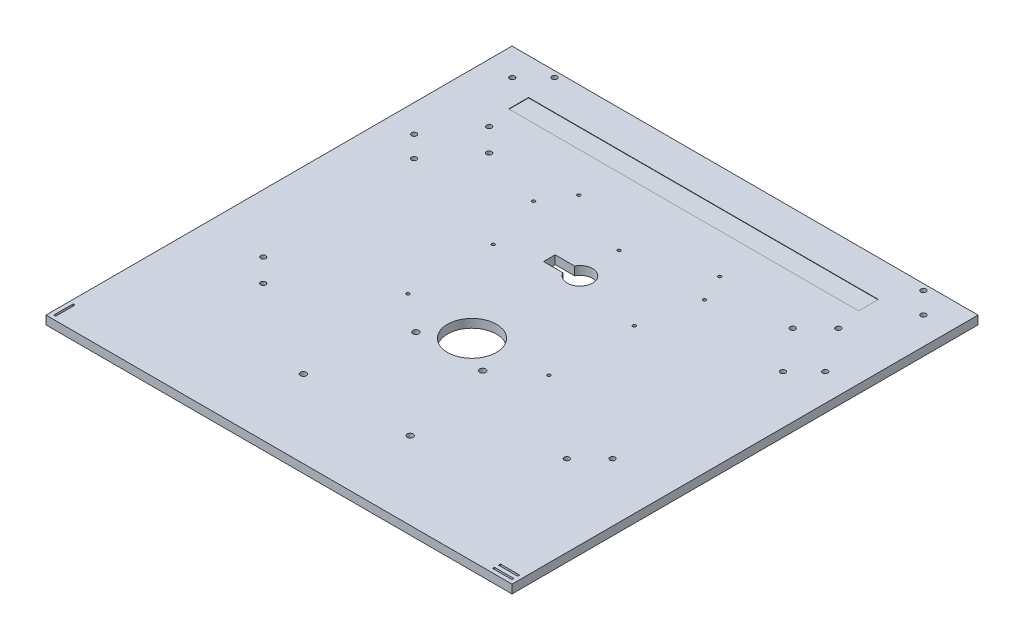
SolidWorks part; units mm, degrees
material "Acrylic (Medium-high impact)"
ref_plane "Front Plane" through (0, 0, 0) normal (0, 0, 1) x (1, 0, 0)
ref_plane "Top Plane" through (0, 0, 0) normal (0, 1, 0) x (1, 0, 0)
ref_plane "Right Plane" through (0, 0, 0) normal (1, 0, 0) x (0, 0, -1)
sketch "Sketch2" plane through (0, 0, 0) normal (0, 1, 0) x (1, 0, 0)
  line L1 (0, 0) -> (304.8, 0)
  line L2 (0, 0) -> (0, 304.8)
  line L3 (0, 304.8) -> (304.8, 304.8)
  line L4 (304.8, 0) -> (304.8, 304.8)
  dimension "D1" = 304.8
  dimension "D2" = 304.8
extrude "Boss-Extrude1" add sketch "Sketch2" along normal blind 5.588
sketch "Sketch4" plane through (0, 5.588, 0) normal (0, 1, 0) x (1, 0, 0)
  line L0 (0, 304.8) -> (0, 0) construction
  line L1 (2.54, 2.54) -> (3.81, 2.54)
  line L2 (2.54, 2.54) -> (2.54, 15.24)
  line L3 (2.54, 15.24) -> (3.81, 15.24)
  line L4 (3.81, 2.54) -> (3.81, 15.24)
  line L5 (2.54, 302.26) -> (3.81, 302.26) construction
  line L6 (2.54, 302.26) -> (2.54, 289.56) construction
  line L7 (2.54, 289.56) -> (3.81, 289.56) construction
  line L8 (3.81, 302.26) -> (3.81, 289.56) construction
  line L9 (6.35, 302.26) -> (7.62, 302.26) construction
  line L10 (6.35, 302.26) -> (6.35, 289.56) construction
  line L11 (6.35, 289.56) -> (7.62, 289.56) construction
  line L12 (7.62, 302.26) -> (7.62, 289.56) construction
  line L13 (304.8, 304.8) -> (0, 304.8) construction
  line L14 (0, 0) -> (304.8, 0) construction
  line L15 (304.8, 0) -> (304.8, 304.8) construction
  line L16 (302.26, 2.54) -> (289.56, 2.54)
  line L17 (302.26, 2.54) -> (302.26, 3.81)
  line L18 (302.26, 3.81) -> (289.56, 3.81)
  line L19 (289.56, 2.54) -> (289.56, 3.81)
  line L20 (302.26, 6.35) -> (289.56, 6.35)
  line L21 (302.26, 6.35) -> (302.26, 7.62)
  line L22 (302.26, 7.62) -> (289.56, 7.62)
  line L23 (289.56, 6.35) -> (289.56, 7.62)
  dimension "D1" = 12.7
  dimension "D2" = 1.27
  dimension "D3" = 2.54
  dimension "D4" = 2.54
  dimension "D5" = 2.54
  dimension "D6" = 2.54
  dimension "D7" = 2.54
  dimension "D8" = 2.54
  dimension "D9" = 2.54
  dimension "D10" = 2.54
extrude "Cut-Extrude1" cut sketch "Sketch4" against normal through all
sketch "Sketch5" plane through (0, 5.588, 0) normal (0, 1, 0) x (1, 0, 0)
  line L0 (0, 304.8) -> (0, 0) construction
  line L1 (34.5465, 268.1122) -> (263.4005, 268.1122)
  line L2 (34.5465, 268.1122) -> (34.5465, 281.0662)
  line L3 (34.5465, 281.0662) -> (263.4005, 281.0662)
  line L4 (263.4005, 268.1122) -> (263.4005, 281.0662)
  line L5 (304.8, 0) -> (304.8, 304.8) construction
  line L6 (304.8, 304.8) -> (0, 304.8) construction
  dimension "D1" = 34.5465
  dimension "D2" = 41.3995
  dimension "D3" = 23.7338
  dimension "D4" = 12.954
extrude "Cut-Extrude2" cut sketch "Sketch5" against normal blind 0.254
sketch "Sketch6" plane through (0, 5.588, 0) normal (0, 1, 0) x (1, 0, 0)
  circle A0 centre (152.48, 126.1263) radius 15.748 construction
  circle A1 centre (152.48, 126.1263) radius 15.748 construction
  circle A2 centre (152.48, 126.1263) radius 16.002
  circle A3 centre (31.75, 300.8321) radius 1.7 construction
  circle A4 centre (17.9387, 287.0209) radius 1.7 construction
  circle A5 centre (273.05, 300.8321) radius 1.7 construction
  circle A6 centre (286.8612, 287.0209) radius 1.7 construction
  circle A7 centre (286.8612, 222.7817) radius 1.7 construction
  circle A8 centre (273.05, 208.9705) radius 1.7 construction
  circle A9 centre (31.75, 208.9705) radius 1.7 construction
  circle A10 centre (17.9388, 222.7817) radius 1.7 construction
  circle A11 centre (31.75, 300.8321) radius 1.7
  circle A12 centre (17.9387, 287.0209) radius 1.7
  circle A13 centre (273.05, 300.8321) radius 1.7
  circle A14 centre (286.8612, 287.0209) radius 1.7
  circle A15 centre (286.8612, 222.7817) radius 1.7
  circle A16 centre (273.05, 208.9705) radius 1.7
  circle A17 centre (31.75, 208.9705) radius 1.7
  circle A18 centre (17.9388, 222.7817) radius 1.7
  circle A19 centre (38.1788, 103.933) radius 1.7 construction
  circle A20 centre (53.133, 88.9788) radius 1.7 construction
  circle A21 centre (251.667, 88.9788) radius 1.7 construction
  circle A22 centre (266.6212, 103.933) radius 1.7 construction
  circle A23 centre (266.6212, 251.667) radius 1.7 construction
  circle A24 centre (251.667, 236.7127) radius 1.7 construction
  circle A25 centre (53.133, 236.7127) radius 1.7 construction
  circle A26 centre (38.1788, 251.667) radius 1.7 construction
  circle A27 centre (38.1788, 103.933) radius 1.7
  circle A28 centre (53.133, 88.9788) radius 1.7
  circle A29 centre (251.667, 88.9788) radius 1.7
  circle A30 centre (266.6212, 103.933) radius 1.7
  circle A31 centre (266.6212, 251.667) radius 1.7
  circle A32 centre (251.667, 236.7127) radius 1.7
  circle A33 centre (53.133, 236.7127) radius 1.7
  circle A34 centre (38.1788, 251.667) radius 1.7
  circle A35 centre (117.555, 50.8216) radius 4.5 construction
  circle A36 centre (187.405, 50.8216) radius 4.5 construction
  circle A37 centre (174.3081, 111.328) radius 4.5 construction
  circle A38 centre (130.6519, 111.328) radius 4.5 construction
  circle A39 centre (117.555, 50.8216) radius 4.5 construction
  circle A40 centre (187.405, 50.8216) radius 4.5 construction
  circle A41 centre (174.3081, 111.328) radius 4.5 construction
  circle A42 centre (130.6519, 111.328) radius 4.5 construction
  circle A43 centre (130.6519, 111.328) radius 1.96
  circle A44 centre (174.3081, 111.328) radius 1.96
  circle A45 centre (187.405, 50.8216) radius 1.96
  circle A46 centre (117.555, 50.8216) radius 1.96
  dimension "D1" = 0.254
  dimension "D2" = 2.54
extrude "Cut-Extrude3" cut sketch "Sketch6" against normal through all
sketch "Sketch7" plane through (0, 5.588, 0) normal (0, 1, 0) x (1, 0, 0)
  line L0 (152.4, 304.8) -> (152.4, 0) construction
  line L1 (304.8, 304.8) -> (0, 304.8) construction
  line L2 (0, 0) -> (304.8, 0) construction
  line L4 (145.0768, 200.66) -> (132.3768, 200.66)
  line L5 (145.0768, 200.66) -> (145.0768, 193.04) construction
  line L6 (145.0768, 193.04) -> (132.3768, 193.04)
  line L7 (132.3768, 200.66) -> (132.3768, 193.04)
  circle A0 centre (152.4, 196.85) radius 8.255 construction
  arc A1 (145.0768, 200.66) -> (145.0768, 193.04) centre (152.4, 196.85) cw
  dimension "D2" = 16.51
  dimension "D1" = 107.95
  dimension "D3" = 7.62
  dimension "D4" = 12.7
extrude "Cut-Extrude4" cut sketch "Sketch7" against normal through all
sketch "Sketch8" plane through (0, 5.588, 0) normal (0, 1, 0) x (1, 0, 0)
  circle A0 centre (94.94, 223.995) radius 0.762 construction
  circle A1 centre (150.82, 223.995) radius 0.762 construction
  circle A2 centre (206.7, 223.995) radius 0.762 construction
  circle A3 centre (94.94, 223.995) radius 0.762 construction
  circle A4 centre (150.82, 223.995) radius 0.762 construction
  circle A5 centre (206.7, 223.995) radius 0.762 construction
  circle A6 centre (206.7, 223.995) radius 1.016
  circle A7 centre (150.82, 223.995) radius 1.016
  circle A8 centre (94.94, 223.995) radius 1.016
  dimension "D1" = 0.254
extrude "Cut-Extrude5" cut sketch "Sketch8" against normal through all
sketch "Sketch9" plane through (0, 5.588, 0) normal (0, 1, 0) x (1, 0, 0)
  circle A0 centre (106.3, 242.18) radius 0.762 construction
  circle A1 centre (106.3, 186.3) radius 0.762 construction
  circle A2 centre (106.3, 130.42) radius 0.762 construction
  circle A3 centre (198.5, 130.42) radius 0.762 construction
  circle A4 centre (198.5, 186.3) radius 0.762 construction
  circle A5 centre (198.5, 242.18) radius 0.762 construction
  circle A6 centre (106.3, 242.18) radius 0.762 construction
  circle A7 centre (106.3, 186.3) radius 0.762 construction
  circle A8 centre (106.3, 130.42) radius 0.762 construction
  circle A9 centre (198.5, 130.42) radius 0.762 construction
  circle A10 centre (198.5, 186.3) radius 0.762 construction
  circle A11 centre (198.5, 242.18) radius 0.762 construction
  circle A12 centre (106.3, 242.18) radius 1.016
  circle A13 centre (106.3, 186.3) radius 1.016
  circle A14 centre (106.3, 130.42) radius 1.016
  circle A15 centre (198.5, 130.42) radius 1.016
  circle A16 centre (198.5, 186.3) radius 1.016
  circle A17 centre (198.5, 242.18) radius 1.016
  dimension "D1" = 0.254
extrude "Cut-Extrude6" cut sketch "Sketch9" against normal through all
equation "\"D8@Sketch4\"=\"D6@Sketch4\""
